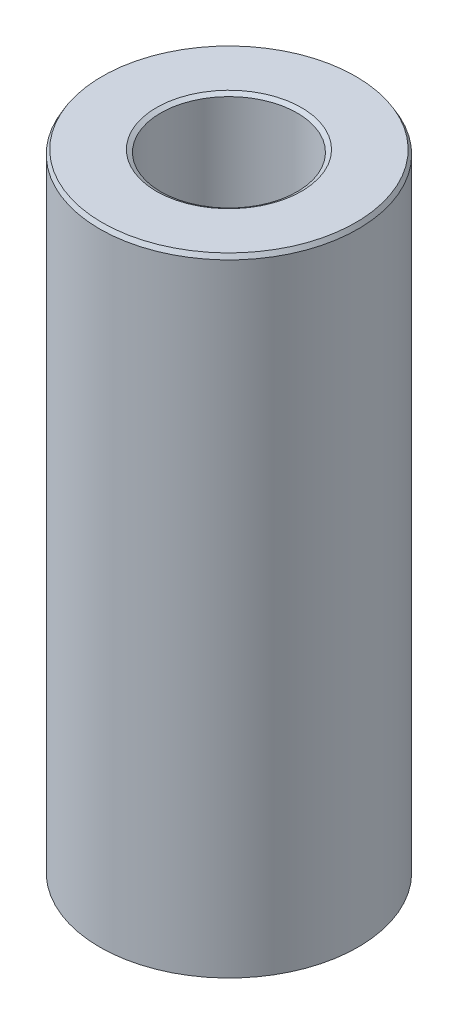
SolidWorks part; units mm, degrees
ref_plane "Front Plane" through (0, 0, 0) normal (0, 0, 1) x (1, 0, 0)
ref_plane "Top Plane" through (0, 0, 0) normal (0, 1, 0) x (1, 0, 0)
ref_plane "Right Plane" through (0, 0, 0) normal (1, 0, 0) x (0, 0, -1)
sketch "Sketch1" plane through (0, 0, 0) normal (0, 1, 0) x (1, 0, 0)
  circle A0 centre (0, 0) radius 17.5
  dimension "SLEEVE_OD" = 35
extrude "Boss-Extrude1" add sketch "Sketch1" along normal blind 85.1412
sketch "Sketch2" plane through (0, 0, 0) normal (0, 1, 0) x (1, 0, 0)
  circle A0 centre (0, 0) radius 9.244
  dimension "BORE_D" = 18.488
extrude "Cut-Extrude1" cut sketch "Sketch2" along normal through all
chamfer "Chamfer1" distance 0.5818 angle 30 4 edges at (0, 85.1412, 9.244) (0, 0, 9.244) (0, 0, 17.5) (0, 85.1412, 17.5) first distance on face at (0, 85.1412, 9.244) first distance on face at (0, 0, 9.244) first distance on face at (0, 85.1412, 17.5)
